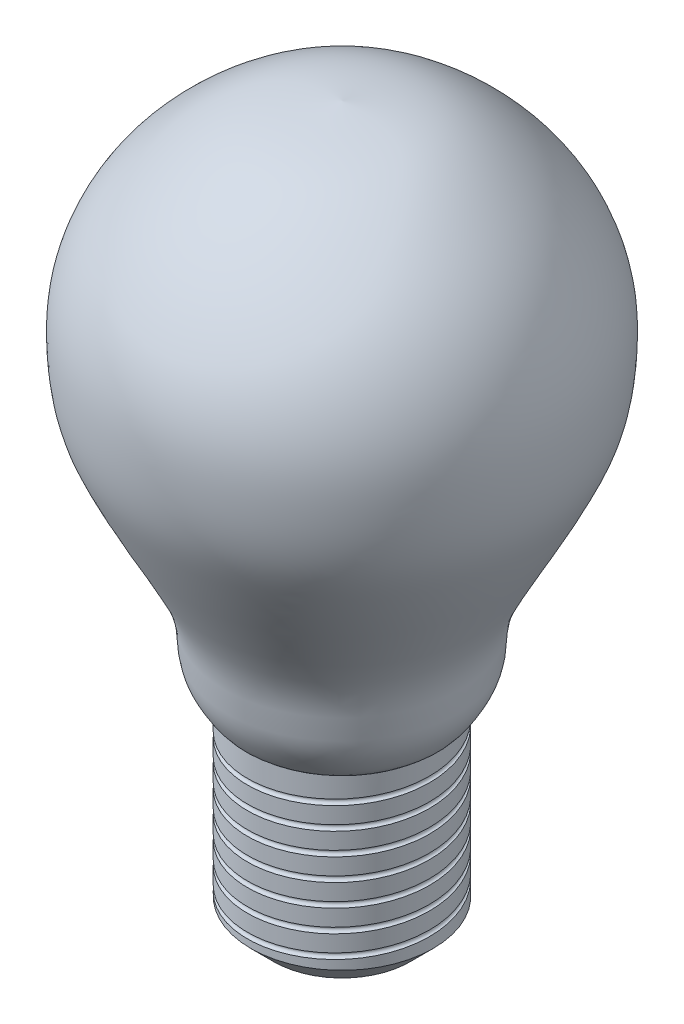
SolidWorks part; units mm, degrees
ref_plane "Front Plane" through (0, 0, 0) normal (0, 0, 1) x (1, 0, 0)
ref_plane "Top Plane" through (0, 0, 0) normal (0, 1, 0) x (1, 0, 0)
ref_plane "Right Plane" through (0, 0, 0) normal (1, 0, 0) x (0, 0, -1)
sketch "Sketch1" plane through (0, 0, 0) normal (0, 1, 0) x (1, 0, 0)
  circle A0 centre (0, 0) radius 20
  dimension "D1" = 40
extrude "Boss-Extrude1" add sketch "Sketch1" along normal blind 40
sketch "Sketch2" plane through (0, 40, 0) normal (0, 1, 0) x (1, 0, 0)
  circle A0 centre (0, 0) radius 19.5
  dimension "D1" = 39
curve "Helix/Spiral1" pitch 4.875 height 39 turns 8
ref_plane "Plane1" through (-19.5, 40, 0) normal (0, -0.0398, -0.9992) x (-1, 0, 0)
sketch "Sketch3" plane through (-19.5, 40, 0) normal (0, -0.0398, -0.9992) x (-1, 0, 0)
  circle A0 centre (0.5, 0) radius 0.625
  dimension "D1" = 1.25
sweep "Cut-Sweep1" cut profiles "Sketch3" path "Helix/Spiral1" align with end faces yes
sketch "Sketch4" plane through (0, 40, 0) normal (0, 1, 0) x (1, 0, 0)
  circle A0 centre (0, 0) radius 20
  dimension "D1" = 40
extrude "Boss-Extrude2" add sketch "Sketch4" along normal blind 2
sketch "Sketch5" plane through (0, 42, 0) normal (0, 1, 0) x (1, 0, 0)
  line L0 (0, 12.1725) -> (0, -7.4351) construction
  line L1 (9.8555, 2.554) -> (-9.8555, 2.554)
  line L2 (-10.6215, 0.9112) -> (-9.02, -0.9974)
  line L3 (-8.4276, -1.3394) -> (0, -2.8255)
  line L4 (8.4276, -1.3394) -> (0, -2.8255)
  line L5 (10.6215, 0.9112) -> (9.02, -0.9974)
  arc A0 (-9.8555, 2.554) -> (-10.6215, 0.9112) centre (-9.8555, 1.554) ccw
  arc A1 (-9.02, -0.9974) -> (-8.4276, -1.3394) centre (-8.254, -0.3546) ccw
  arc A2 (9.02, -0.9974) -> (8.4276, -1.3394) centre (8.254, -0.3546) cw
  arc A3 (9.8555, 2.554) -> (10.6215, 0.9112) centre (9.8555, 1.554) cw
  point P3 (8.7861, -1.2762)
  point P9 (-12, 2.554)
  point P12 (-8.7861, -1.2762)
  point P19 (0, 2.554)
  point P20 (12, 2.554)
  dimension "D5" = 1
  dimension "D1" = 12
  dimension "D2" = 50
  dimension "D3" = 5
  dimension "D4" = 140
extrude "Boss-Extrude3" add sketch "Sketch5" along normal blind 20
sketch "Sketch6" plane through (0, 0, -2.554) normal (0, 0, -1) x (-1, 0, 0)
  circle A0 centre (0, 53.5203) radius 3
  dimension "D1" = 6
extrude "Cut-Extrude1" cut sketch "Sketch6" against normal through all
sketch "Sketch7" plane through (0, 62, 0) normal (0, 1, 0) x (1, 0, 0)
  circle A0 centre (0, 0) radius 2.5
  dimension "D1" = 5
extrude "Boss-Extrude4" add sketch "Sketch7" along normal blind 25
sketch "Sketch8" plane through (0, 87, 0) normal (0, 1, 0) x (1, 0, 0)
  circle A0 centre (0, 0) radius 2.5
  circle A1 centre (0, 0) radius 3
  dimension "D1" = 5
  dimension "D2" = 6
extrude "Boss-Extrude5" add sketch "Sketch8" along normal blind 2 separate body
fillet "Fillet3" radius 10 2 edges at (0, 46.2601, 2.8255) (0, 59.2601, 2.8255)
fillet "Fillet1" radius 1 2 edges at (0, 87, 3) (0, 89, 3)
ref_plane "Plane2" through (0, 0, -2) normal (0, 0, 1) x (1, 0, 0)
sketch "Sketch10" plane through (0, 0, -2) normal (0, 0, 1) x (1, 0, 0)
  line L0 (0, 91.877) -> (0, 40.6264) construction
  line L1 (-4.418, 59.6619) -> (-22.7325, 98.9375)
  dimension "D1" = 25
ref_plane "Plane3" through (-22.7325, 98.9375, -2) normal (-0.4226, 0.9063, 0) x (0.9063, 0.4226, 0)
sketch "Sketch11" plane through (-22.7325, 98.9375, -2) normal (-0.4226, 0.9063, 0) x (0.9063, 0.4226, 0)
  circle A0 centre (0, 0) radius 0.3
  dimension "D1" = 0.6
sweep "Sweep1" add profiles "Sketch11" path "Sketch10"
mirror "Mirror1" about plane through (0, 0, 0) normal (1, 0, 0) of "Sweep1"
sketch "Sketch12" plane through (0, 0, 0) normal (0, 0, 1) x (1, 0, 0)
  line L0 (-940.429, 797.843) -> (-140.429, 797.843) construction
  line L1 (0, 0) -> (0, 176.8158) construction
sketch "Sketch13" plane through (0, 0, 0) normal (0, 0, 1) x (1, 0, 0)
  line L1 (0, 42) -> (-20, 42)
  line L2 (0, 42) -> (0, 156.1705) construction
  spline S0 degree 3 poles (-20, 42) (-21.1758, 42.7717) (-22.6615, 45.044) (-24.6652, 48.568) (-25.6204, 52.5566) (-25.6572, 57.0336) (-26.5676, 61.6526) (-28.437, 66.2208) (-30.6053, 70.2374) (-33.1523, 75.0267) (-36.5276, 81.1207) (-40.3982, 88.6922) (-44.6865, 98.1243) (-46.007, 108.1889) (-45.8572, 117.8827) (-43.4737, 127.42) (-38.1281, 137.3543) (-28.926, 146.568) (-16.4924, 154.7222) (-5.7897, 155.5318) (0, 156.1705) knots 0 0 0 0 0.028166 0.055101 0.082927 0.111038 0.146839 0.178657 0.211958 0.240453 0.28996 0.35482 0.415126 0.501339 0.560228 0.613245 0.701576 0.78762 0.878872 1 1 1 1
surface "Surface-Revolve3" sketch "Sketch13" parameters "D1"=360
sketch "Sketch14" plane through (0, 0, 0) normal (0, -1, 0) x (1, 0, 0)
  circle A0 centre (0, 0) radius 4
  dimension "D1" = 8
extrude "Boss-Extrude6" add sketch "Sketch14" along normal blind 3
chamfer "Chamfer1" distance 5 angle 45 1 edges at (0, 0, 20)
sketch "Sketch15" plane through (0, 0, -2) normal (0, 0, 1) x (1, 0, 0)
  line L0 (-2, 88.134) -> (-8.3505, 103.3871)
  line L1 (-3, 88.134) -> (3, 88.134) construction
ref_plane "Plane4" through (-8.3505, 103.3871, -2) normal (-0.3844, 0.9232, 0) x (0.9232, 0.3844, 0)
sketch "Sketch16" plane through (-8.3505, 103.3871, -2) normal (-0.3844, 0.9232, 0) x (0.9232, 0.3844, 0)
  circle A0 centre (0, 0) radius 0.15
  dimension "D1" = 0.3
sweep "Sweep2" add profiles "Sketch16" path "Sketch15"
mirror "Mirror2" about plane through (0, 0, 0) normal (1, 0, 0) of "Sweep2"
sketch "Sketch17" plane through (0, 0, -2) normal (0, 0, 1) x (1, 0, 0)
  spline S0 degree 3 poles (-22.6777, 98.7762) (-18.4109, 101.6336) (-8.0098, 103.8059) (7.8858, 104.6396) (18.0254, 100.7505) (22.6481, 98.7762) knots 0 0 0 0 0.319926 0.676007 1 1 1 1
ref_plane "Plane5" through (-22.6777, 98.7762, -2) normal (0.8309, 0.5564, 0) x (0, 0, -1)
sketch "Sketch18" plane through (-22.6777, 98.7762, -2) normal (0.8309, 0.5564, 0) x (0, 0, -1)
  circle A0 centre (0, 0) radius 0.1
  dimension "D1" = 0.2
sweep "Sweep6" add profiles "Sketch18" path "Sketch17"
chamfer "Chamfer2" distance 2 angle 45 1 edges at (0, -3, -4)
fillet "Fillet4" radius 1 1 edges at (0, -3, -2)
